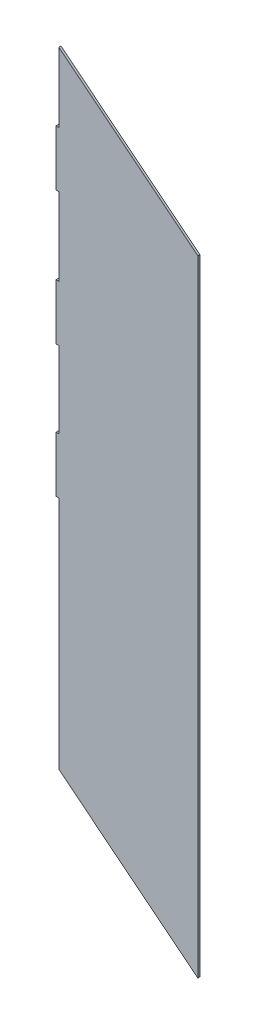
SolidWorks part; units mm, degrees
material "1345 Alloy"
ref_plane "Front Plane" through (0, 0, 0) normal (0, 0, 1) x (1, 0, 0)
ref_plane "Top Plane" through (0, 0, 0) normal (0, 1, 0) x (1, 0, 0)
ref_plane "Right Plane" through (0, 0, 0) normal (1, 0, 0) x (0, 0, -1)
sketch "Sketch1" plane through (0, 0, 0) normal (0, 0, 1) x (1, 0, 0)
  line L0 (0, -152.1368) -> (0, 297.8632)
  line L1 (0, 297.8632) -> (100, 217.8632)
  line L2 (100, 217.8632) -> (100, -232.1368)
  line L3 (0, -152.1368) -> (100, -232.1368)
  dimension "D1" = 100
  dimension "D2" = 80
extrude "Boss-Extrude1" add sketch "Sketch1" along normal blind 1.5
sketch "Sketch7" plane through (0, 0, 0) normal (-1, 0, 0) x (0, 0, 1)
  line L0 (0, 247.8632) -> (1.5, 247.8632)
  line L3 (1.5, 247.8632) -> (1.5, 207.8632)
  line L4 (1.5, 207.8632) -> (0, 207.8632)
  line L5 (0, 207.8632) -> (0, 247.8632)
  line L8 (0, 151.9834) -> (1.5, 151.9834)
  line L9 (0, 151.9834) -> (0, 111.9834)
  line L10 (0, 111.9834) -> (1.5, 111.9834)
  line L11 (1.5, 151.9834) -> (1.5, 111.9834)
  line L12 (0, 16.9834) -> (1.5, 16.9834)
  line L13 (0, 16.9834) -> (0, 56.9834)
  line L14 (0, 56.9834) -> (1.5, 56.9834)
  line L15 (1.5, 16.9834) -> (1.5, 56.9834)
  line L20 (1.5, 297.8632) -> (0, 297.8632) construction
  dimension "D1" = 40
  dimension "D2" = 50
  dimension "D3" = 40
  dimension "D4" = 40
  dimension "D6" = 55
extrude "Boss-Extrude3" add sketch "Sketch7" along normal blind 2
